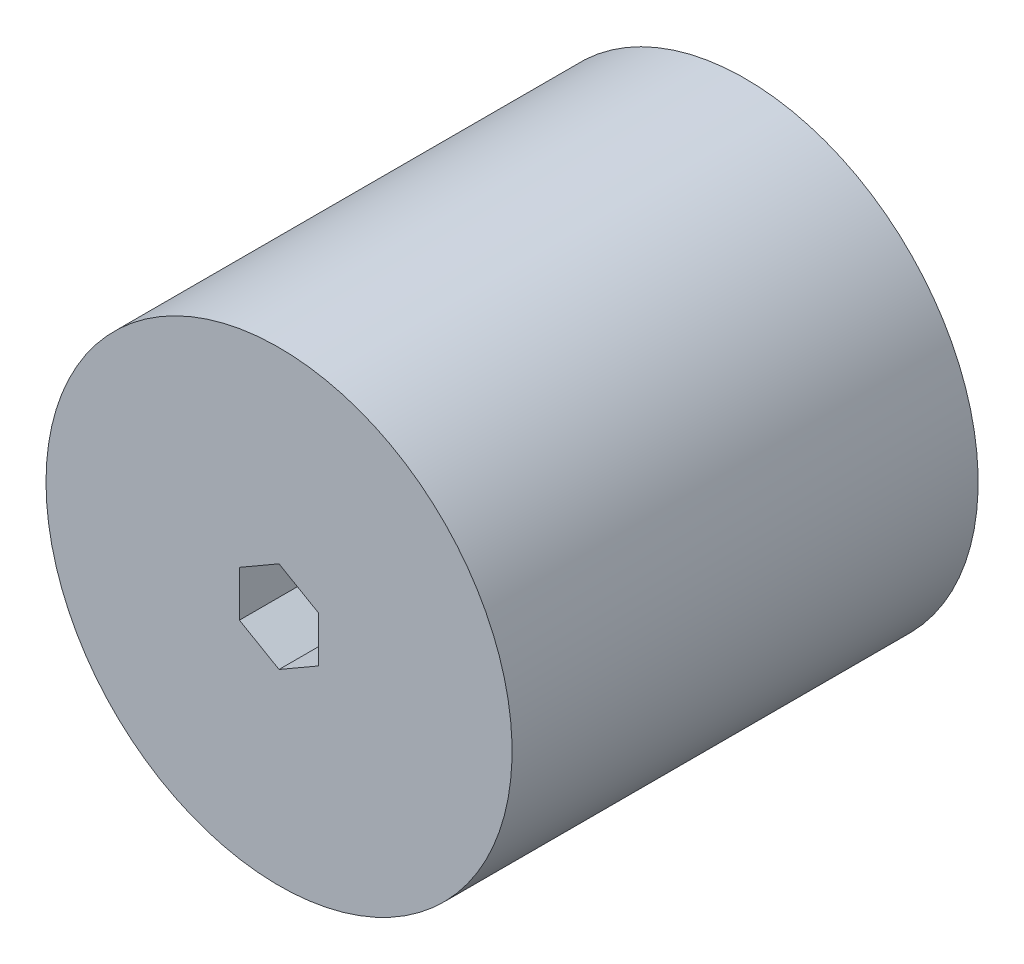
SolidWorks part; units mm, degrees
material "PET"
ref_plane "Front Plane" through (0, 0, 0) normal (0, 0, 1) x (1, 0, 0)
ref_plane "Top Plane" through (0, 0, 0) normal (0, 1, 0) x (1, 0, 0)
ref_plane "Right Plane" through (0, 0, 0) normal (1, 0, 0) x (0, 0, -1)
sketch "Sketch1" plane through (0, 0, 0) normal (0, 0, 1) x (1, 0, 0)
  line L1 (0, 7.479) -> (-6.477, 3.7395)
  line L2 (-6.477, 3.7395) -> (-6.477, -3.7395)
  line L3 (-6.477, -3.7395) -> (0, -7.479)
  line L4 (0, -7.479) -> (6.477, -3.7395)
  line L5 (6.477, -3.7395) -> (6.477, 3.7395)
  line L6 (6.477, 3.7395) -> (0, 7.479)
  circle A0 centre (0, 0) radius 38.1
  circle A1 centre (0, 0) radius 6.477 construction
  dimension "D1" = 76.2
  dimension "D2" = 12.954
extrude "Boss-Extrude1" add sketch "Sketch1" along normal blind 76.2
